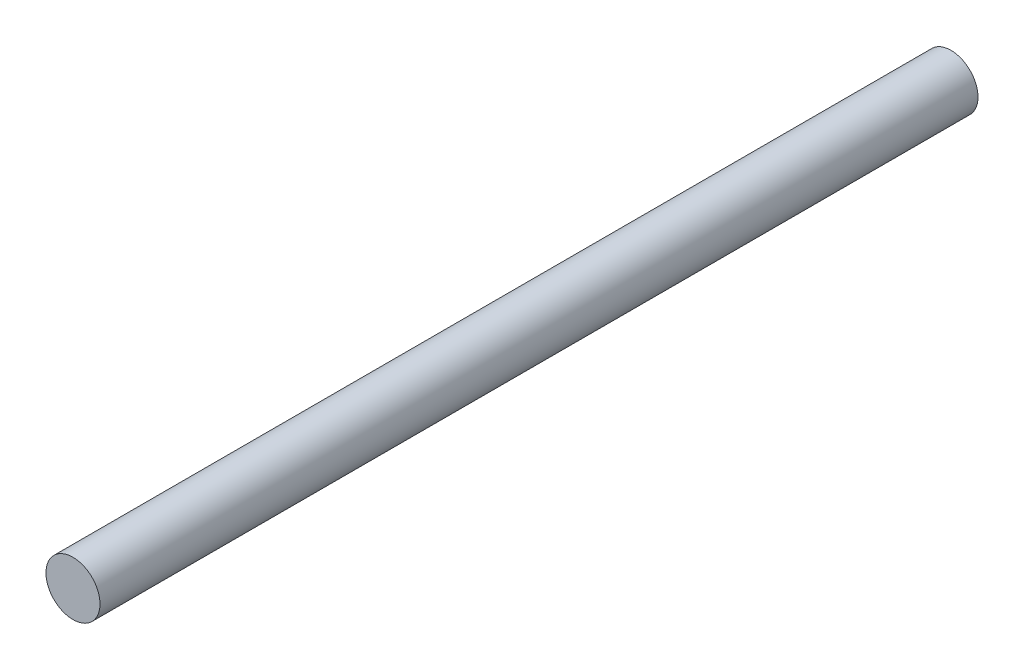
SolidWorks part; units mm, degrees
ref_plane "Front Plane" through (0, 0, 0) normal (0, 0, 1) x (1, 0, 0)
ref_plane "Top Plane" through (0, 0, 0) normal (0, 1, 0) x (1, 0, 0)
ref_plane "Right Plane" through (0, 0, 0) normal (1, 0, 0) x (0, 0, -1)
sketch "Sketch2" plane through (0, 0, 0) normal (0, 0, 1) x (1, 0, 0)
  circle A0 centre (0, 0) radius 4
  dimension "D1" = 8
extrude "Boss-Extrude1" add sketch "Sketch2" along normal blind 130
